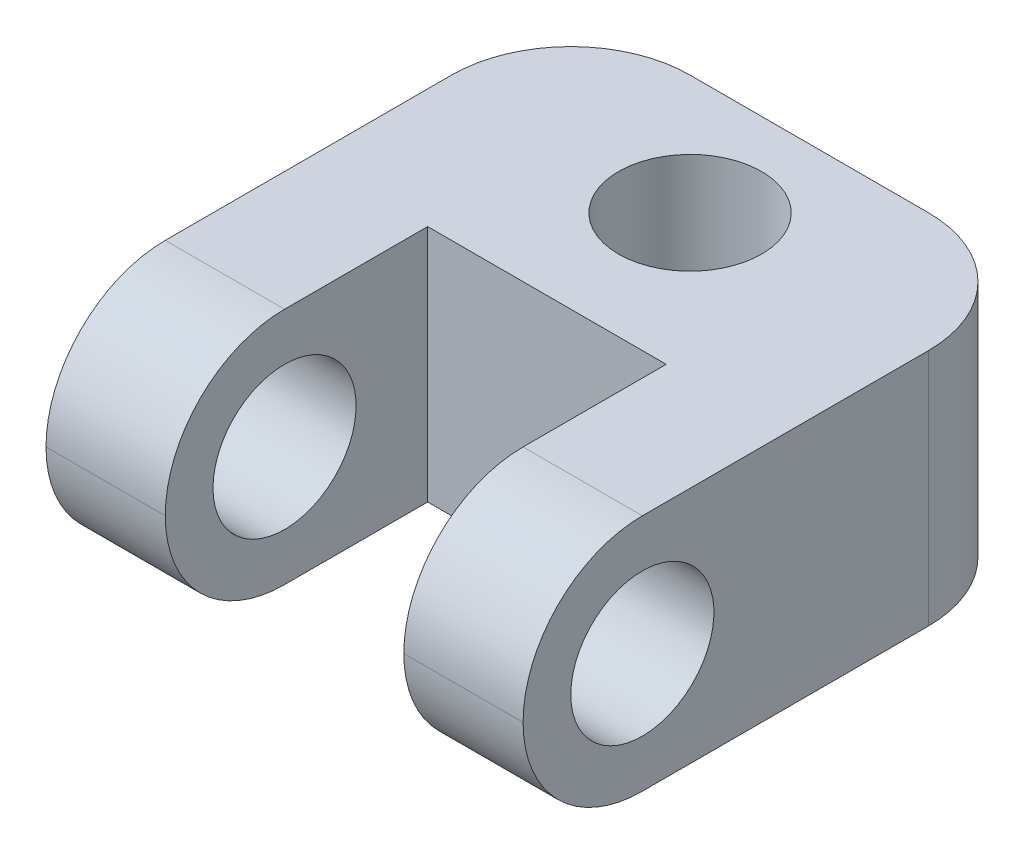
SolidWorks part; units mm, degrees
ref_plane "Front Plane" through (0, 0, 0) normal (0, 0, 1) x (1, 0, 0)
ref_plane "Top Plane" through (0, 0, 0) normal (0, 1, 0) x (1, 0, 0)
ref_plane "Right Plane" through (0, 0, 0) normal (1, 0, 0) x (0, 0, -1)
sketch "Sketch1" plane through (0, 0, 0) normal (0, 1, 0) x (1, 0, 0)
  line L1 (-5, 5.5) -> (5, 5.5)
  line L2 (-5, 5.5) -> (-5, -5.5)
  line L3 (-5, -5.5) -> (5, -5.5)
  line L4 (5, 5.5) -> (5, -5.5)
  line L5 (-5, 5.5) -> (5, -5.5) construction
  line L6 (-5, -5.5) -> (5, 5.5) construction
  point P0 (0, 0)
  dimension "D1" = 11
  dimension "D2" = 10
extrude "Boss-Extrude1" add sketch "Sketch1" along normal blind 5
sketch "Sketch3" plane through (0, 5, 0) normal (0, 1, 0) x (1, 0, 0)
  line L0 (-5, -5.5) -> (5, -5.5) construction
  line L1 (-2.5, 0) -> (2.5, 0)
  line L2 (-2.5, 0) -> (-2.5, -5.5)
  line L3 (-2.5, -5.5) -> (2.5, -5.5)
  line L4 (2.5, 0) -> (2.5, -5.5)
  line L5 (-2.5, 0) -> (2.5, -5.5) construction
  line L6 (-2.5, -5.5) -> (2.5, 0) construction
  line L7 (-5, 5.5) -> (-5, -5.5) construction
  point P0 (0, -2.75)
  dimension "D1" = 2.5
  dimension "D2" = 5
  dimension "D3" = 5.5
extrude "Cut-Extrude1" cut sketch "Sketch3" against normal blind 5
sketch "Sketch4" plane through (0, 5, 0) normal (0, 1, 0) x (1, 0, 0)
  line L0 (5, 5.5) -> (-5, 5.5) construction
  circle A0 centre (0, 3) radius 1.5
  dimension "D1" = 3
  dimension "D2" = 2.5
extrude "Cut-Extrude2" cut sketch "Sketch4" against normal blind 5
sketch "Sketch5" plane through (-5, 0, 0) normal (-1, 0, 0) x (0, 0, 1)
  line L0 (5.5, 5) -> (5.5, 0) construction
  line L1 (-5.5, 0) -> (5.5, 0) construction
  circle A0 centre (3, 2.5) radius 1.5
  dimension "D1" = 3
  dimension "D2" = 2.5
  dimension "D3" = 2.5
extrude "Cut-Extrude3" cut sketch "Sketch5" against normal blind 10
fillet "Fillet1" radius 2.5 4 edges at (3.75, 0, 5.5) (3.75, 5, 5.5) (-3.75, 0, 5.5) (-3.75, 5, 5.5)
fillet "Fillet2" radius 2.5 2 edges at (5, 2.5, -5.5) (-5, 2.5, -5.5)
